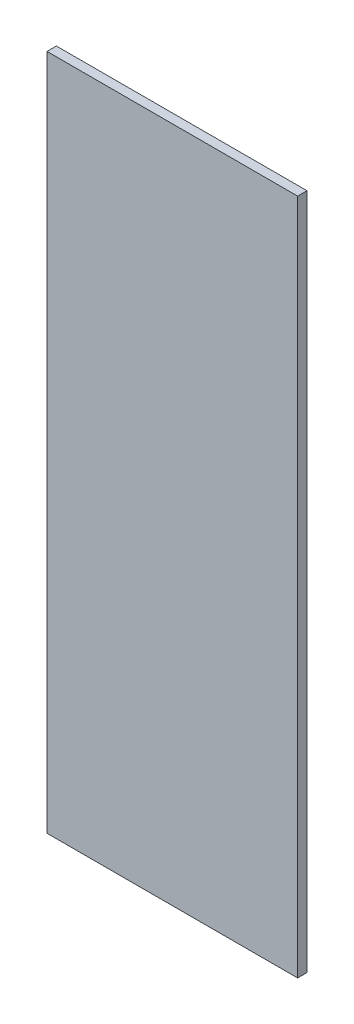
SolidWorks part; units mm, degrees
ref_plane "Спереди" through (0, 0, 0) normal (0, 0, 1) x (1, 0, 0)
ref_plane "Сверху" through (0, 0, 0) normal (0, 1, 0) x (1, 0, 0)
ref_plane "Справа" through (0, 0, 0) normal (1, 0, 0) x (0, 0, -1)
sketch "Sketch1" plane through (0, 0, 0) normal (0, 0, 1) x (1, 0, 0)
  line L1 (-53.6, 0) -> (53.6, 0)
  line L2 (-53.6, 0) -> (-53.6, -289.6)
  line L3 (-53.6, -289.6) -> (53.6, -289.6)
  line L4 (53.6, 0) -> (53.6, -289.6)
  point P4 (0, -289.6)
  point P5 (0, 0)
extrude "Extrude1" add sketch "Sketch1" along normal blind 4
equation "\"thickness\"=4"
equation "\"D1@Extrude1\"=\"thickness\""
